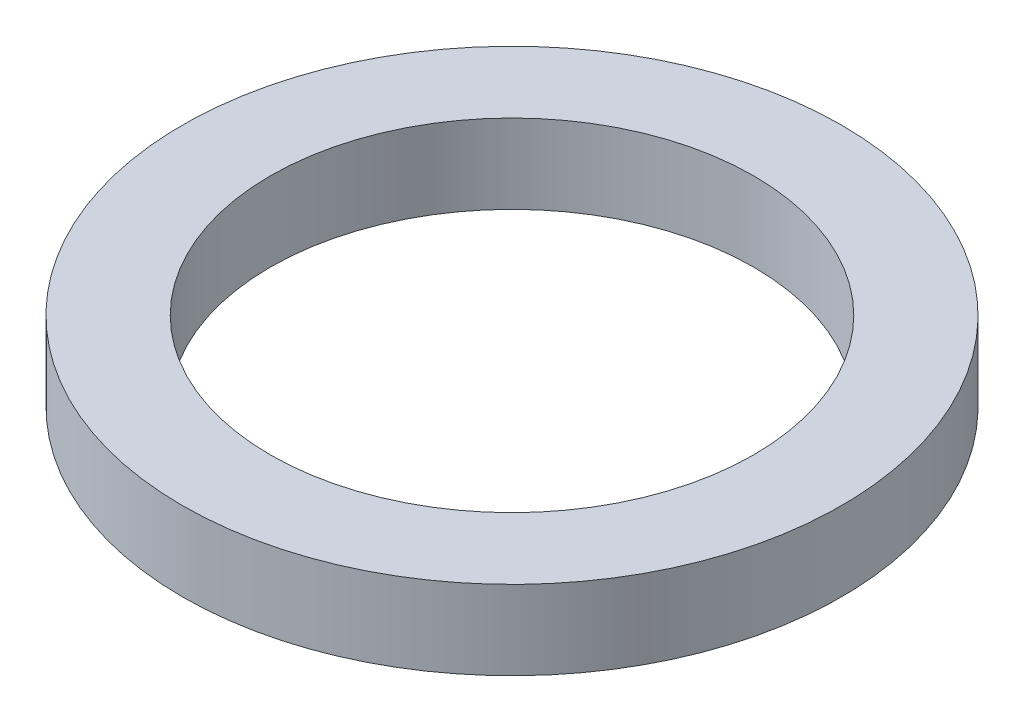
SolidWorks part; units mm, degrees
ref_plane "Front Plane" through (0, 0, 0) normal (0, 0, 1) x (1, 0, 0)
ref_plane "Top Plane" through (0, 0, 0) normal (0, 1, 0) x (1, 0, 0)
ref_plane "Right Plane" through (0, 0, 0) normal (1, 0, 0) x (0, 0, -1)
sketch "Sketch1" plane through (0, 0, 0) normal (0, 1, 0) x (1, 0, 0)
  circle A0 centre (0, 0) radius 37.5
  dimension "FLANGE_OD" = 75
extrude "Boss-Extrude1" add sketch "Sketch1" along normal blind 9
sketch "Sketch2" plane through (0, 0, 0) normal (0, 1, 0) x (1, 0, 0)
  circle A0 centre (0, 0) radius 27.5
  dimension "BORE_D" = 55
extrude "Cut-Extrude1" cut sketch "Sketch2" along normal through all
sketch "Sketch3" plane through (0, 9, 0) normal (0, 1, 0) x (1, 0, 0)
  circle A0 centre (0, 0) radius 15.7876 construction
  circle A1 centre (-15.7876, 0) radius 1.5401
  dimension "BOLT_D" = 3.0801
  dimension "BOLT_PCD" = 31.5753
extrude "Cut-Extrude2" cut sketch "Sketch3" against normal blind 6.7336 rebuild error yes
pattern_circular "CirPattern1" count 4 over 360 rebuild error yes
